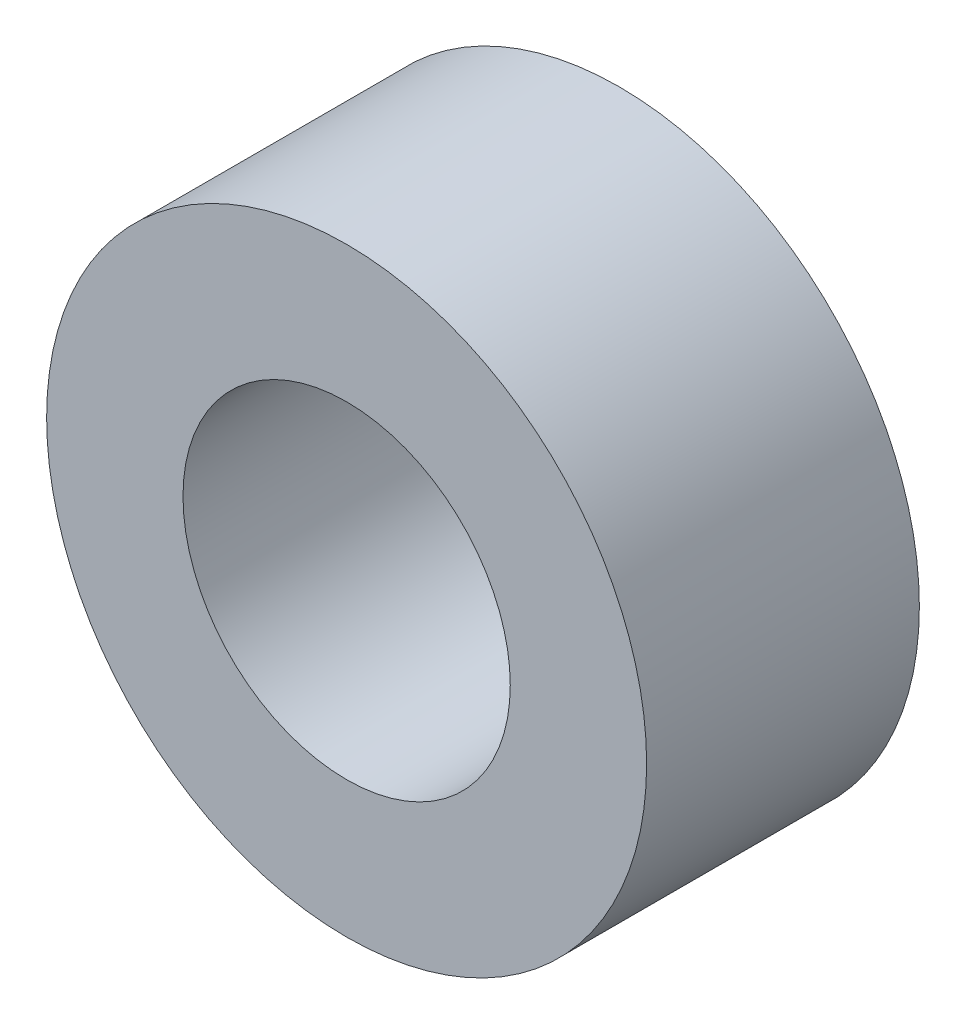
SolidWorks part; units mm, degrees
ref_plane "Front Plane" through (0, 0, 0) normal (0, 0, 1) x (1, 0, 0)
ref_plane "Top Plane" through (0, 0, 0) normal (0, 1, 0) x (1, 0, 0)
ref_plane "Right Plane" through (0, 0, 0) normal (1, 0, 0) x (0, 0, -1)
sketch "Sketch1" plane through (0, 0, 0) normal (0, 0, 1) x (1, 0, 0)
  circle A0 centre (0, 0) radius 15
  circle A1 centre (0, 0) radius 27.5
  dimension "D1" = 55
  dimension "D2" = 30
extrude "Boss-Extrude1" add sketch "Sketch1" against normal blind 25
